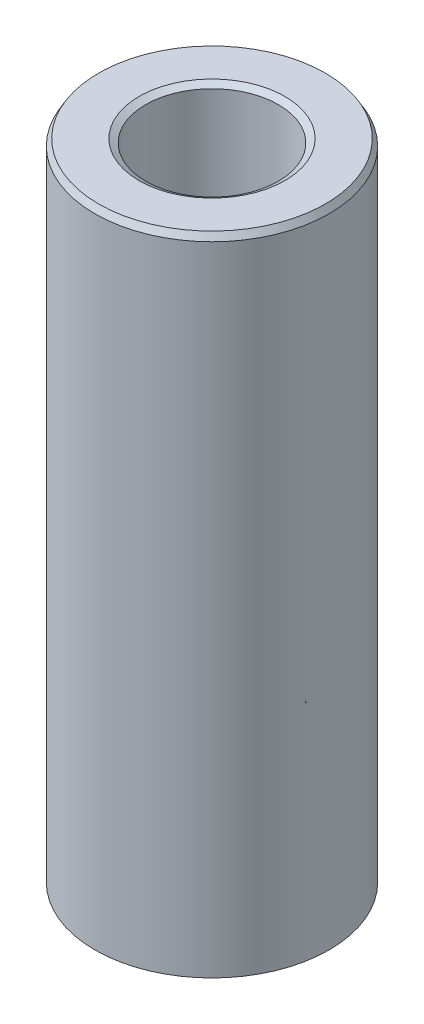
SolidWorks part; units mm, degrees
ref_plane "Front Plane" through (0, 0, 0) normal (0, 0, 1) x (1, 0, 0)
ref_plane "Top Plane" through (0, 0, 0) normal (0, 1, 0) x (1, 0, 0)
ref_plane "Right Plane" through (0, 0, 0) normal (1, 0, 0) x (0, 0, -1)
sketch "Sketch1" plane through (0, 0, 0) normal (0, 1, 0) x (1, 0, 0)
  circle A0 centre (0, 0) radius 57.5
  dimension "SLEEVE_OD" = 115
extrude "Boss-Extrude1" add sketch "Sketch1" along normal blind 317.9786
sketch "Sketch2" plane through (0, 0, 0) normal (0, 1, 0) x (1, 0, 0)
  circle A0 centre (0, 0) radius 32.5735
  dimension "BORE_D" = 65.1469
extrude "Cut-Extrude1" cut sketch "Sketch2" along normal through all
chamfer "Chamfer1" distance 3.2231 angle 30 4 edges at (0, 317.9786, 32.5735) (0, 0, 32.5735) (0, 0, 57.5) (0, 317.9786, 57.5) first distance on face at (0, 317.9786, 32.5735) first distance on face at (0, 0, 32.5735) first distance on face at (0, 317.9786, 57.5)
